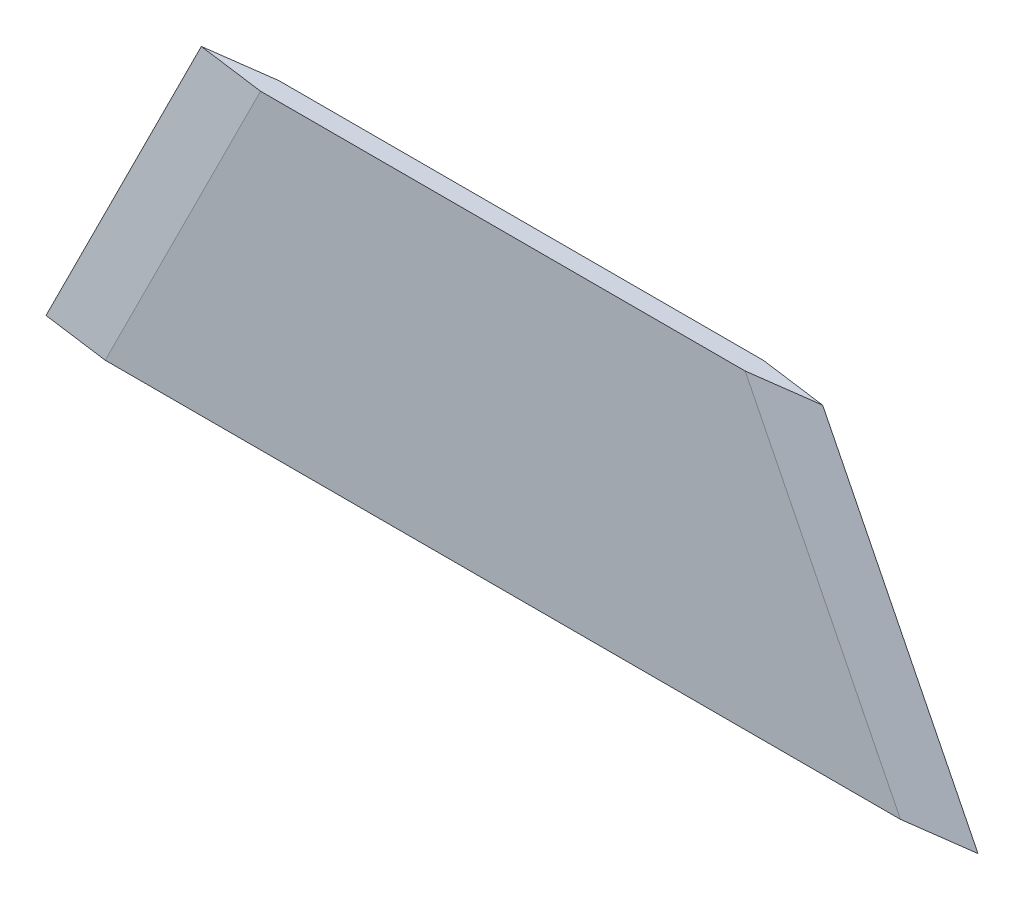
SolidWorks part; units mm, degrees
material "A-Glass Fiber"
ref_plane "Front Plane" through (0, 0, 0) normal (0, 0, 1) x (1, 0, 0)
ref_plane "Top Plane" through (0, 0, 0) normal (0, 1, 0) x (1, 0, 0)
ref_plane "Right Plane" through (0, 0, 0) normal (1, 0, 0) x (0, 0, -1)
sketch "Sketch1" plane through (0, 0, 0) normal (0, 0, 1) x (1, 0, 0)
  line L0 (0, 0) -> (152.4, 0) construction
  line L1 (0, 0) -> (25.4, 50.8)
  line L2 (25.4, 50.8) -> (127, 50.8)
  line L3 (127, 50.8) -> (152.4, 0)
  line L4 (0, 0) -> (152.4, 0)
  dimension "D1" = 101.6
  dimension "D2" = 152.4
  dimension "D3" = 50.8
extrude "Boss-Extrude1" add sketch "Sketch1" along normal mid plane 2.9972
chamfer "Chamfer1" distance 1.4986 distance2 10 2 edges at (12.7, 25.4, -1.4986) (12.7, 25.4, 1.4986) first distance on face at (12.7, 25.4, 0)
chamfer "Chamfer2" distance 1.4986 distance2 10 2 edges at (139.7, 25.4, -1.4986) (139.7, 25.4, 1.4986) first distance on face at (139.7, 25.4, 0)
